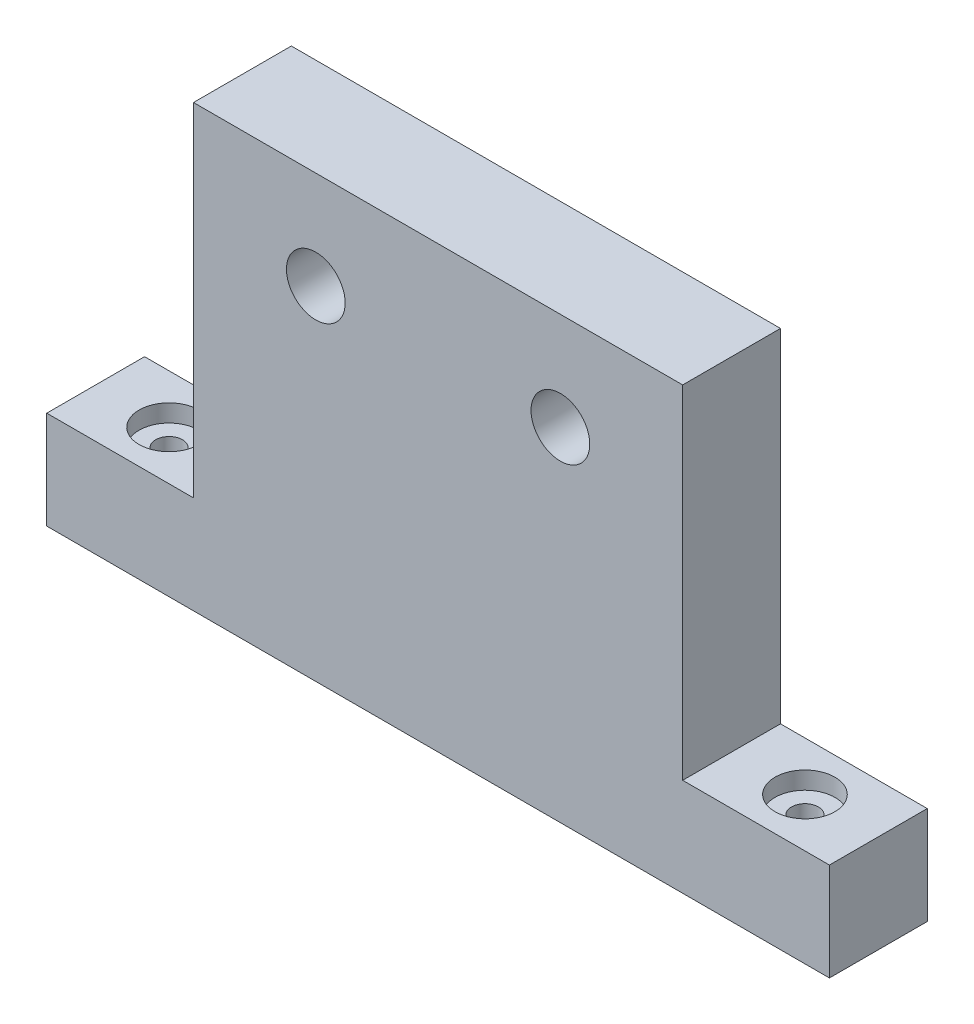
SolidWorks part; units mm, degrees
ref_plane "Front Plane" through (0, 0, 0) normal (0, 0, 1) x (1, 0, 0)
ref_plane "Top Plane" through (0, 0, 0) normal (0, 1, 0) x (1, 0, 0)
ref_plane "Right Plane" through (0, 0, 0) normal (1, 0, 0) x (0, 0, -1)
sketch "Sketch2" plane through (0, 0, 0) normal (0, 0, 1) x (1, 0, 0)
  line L0 (0, 0) -> (0, 90) construction
  line L1 (80, 0) -> (-80, 0)
  line L2 (-80, 0) -> (-80, 20)
  line L3 (-80, 20) -> (-50, 20)
  line L4 (-50, 20) -> (-50, 90)
  line L5 (-50, 90) -> (0, 90)
  line L10 (50, 90) -> (0, 90)
  line L11 (50, 20) -> (50, 90)
  line L12 (80, 20) -> (50, 20)
  line L13 (80, 0) -> (80, 20)
  circle A0 centre (-25, 70) radius 6
  circle A1 centre (25, 70) radius 6
  point P7 (-25, 90)
  dimension "D5" = 12
  dimension "D7" = 50
  dimension "D6" = 70
  dimension "D1" = 90
  dimension "D2" = 80
  dimension "D3" = 30
  dimension "D4" = 20
extrude "Corpo - Furos 12mm" add sketch "Sketch2" along normal blind 20
hole_wizard "Furos Ø6mm" positions "Sketch4" profile "Sketch5" counterbore size "M5" standard "ANSI Metric" end condition through all
sketch "Sketch4" plane through (0, 20, 0) normal (0, 1, 0) x (1, 0, 0)
  line L0 (-65, -10) -> (65, -10) construction
  line L2 (-50, -20) -> (-80, -20) construction
  line L3 (-80, -20) -> (-80, 0) construction
  point P0 (-65, -10)
  point P2 (65, -10)
  dimension "D1" = 10
  dimension "D2" = 15
  dimension "D3" = 130
sketch "Sketch5" plane through (-65, 20, 10) normal (1, 0, 0) x (0, 0, 1)
  line L0 (0, 0) -> (0, 20)
  line L1 (0, 20) -> (2.75, 20)
  line L3 (2.75, 20) -> (2.75, 3.58)
  line L4 (2.75, 3.58) -> (6.12, 3.58)
  line L5 (6.12, 3.58) -> (6.12, 0)
  line L7 (6.12, 0) -> (0, 0)
  line L11 (0, -6.35) -> (0, 107.95) construction
  dimension "Thru Hole Dia." = 5.5
  dimension "Thru Hole Depth" = 20
  dimension "C'Bore Dia." = 12.24
  dimension "C'Bore Depth" = 3.58
